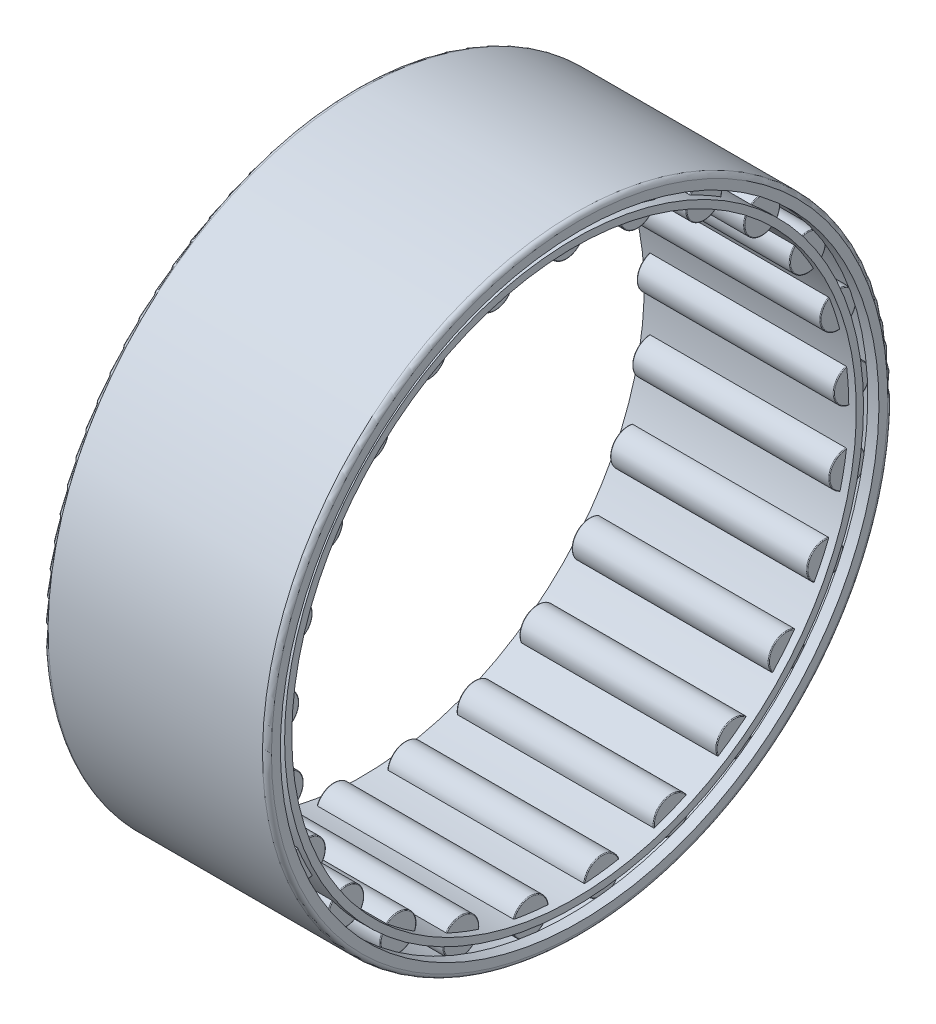
SolidWorks part; units mm, degrees
ref_plane "Plane1" through (0, 0, 0) normal (0, 0, 1) x (1, 0, 0)
ref_plane "Plane2" through (0, 0, 0) normal (0, 1, 0) x (1, 0, 0)
ref_plane "Plane3" through (0, 0, 0) normal (1, 0, 0) x (0, 0, -1)
sketch "Clipboard" plane through (0, 0, 0) normal (0, 0, 1) x (1, 0, 0)
  line L0 (-10, 0) -> (10, 0) construction
  line L1 (0, 0) -> (20.2657, -9.45)
  line L2 (0, 0) -> (36.8323, 17.1752)
  line L3 (0, 0) -> (20.2657, -9.45)
  line L4 (0, 0) -> (-76.2, -2.661)
  dimension "BallCLRad" = 40.64
  dimension "Bore" = 76.2
sketch "InnRacSke" plane through (0, 0, 0) normal (0, 0, 1) x (1, 0, 0)
  line L0 (-14.2875, 42.545) -> (-15.875, 42.545)
  line L1 (-15.875, 42.545) -> (-15.875, 43.815)
  line L2 (-15.24, 44.45) -> (15.24, 44.45)
  line L4 (15.875, 43.815) -> (15.875, 42.545)
  line L5 (15.875, 42.545) -> (14.2875, 42.545)
  line L6 (14.2875, 42.545) -> (14.2875, 43.18)
  line L7 (14.2875, 43.18) -> (-14.2875, 43.18)
  line L8 (-14.2875, 43.18) -> (-14.2875, 42.545)
  line L9 (-31.75, 0) -> (31.75, 0) construction
  arc A0 (-15.875, 43.815) -> (-15.24, 44.45) centre (-15.24, 43.815) cw
  arc A2 (15.24, 44.45) -> (15.875, 43.815) centre (15.24, 43.815) cw
  dimension "D1" = 86.36
revolve "Race" add sketch "InnRacSke" angle 360 about L9 reverse direction yes
sketch "RolDetSke" plane through (0, 0, 0) normal (0, 0, 1) x (1, 0, 0)
  line L0 (-14.0018, 43.0906) -> (-14.0017, 40.64)
  line L1 (-14.0017, 40.64) -> (14.0017, 40.64)
  line L2 (14.0017, 40.64) -> (14.0018, 43.0906)
  line L3 (13.8996, 43.1927) -> (-13.8996, 43.1927)
  line L4 (-28.575, 40.64) -> (28.575, 40.64) construction
  arc A0 (14.0018, 43.0906) -> (13.8996, 43.1927) centre (13.8996, 43.0906) ccw
  arc A1 (-13.8996, 43.1927) -> (-14.0018, 43.0906) centre (-13.8996, 43.0906) ccw
  dimension "Roller_length" = 28.0035
revolve "RollerDetailed" add sketch "RolDetSke" angle 360 about L4 reverse direction yes
ref_axis "Axis1" through (-50, 0, 0) along (1, 0, 0)
sketch "CagSpiSke" plane through (0, 0, 0) normal (0, 0, 1) x (1, 0, 0)
  line L0 (15.0812, 40.1295) -> (15.0812, 41.1505)
  line L1 (15.0812, 41.1505) -> (-15.0813, 41.1505)
  line L2 (-15.0813, 41.1505) -> (-15.0813, 40.1295)
  line L3 (-15.0813, 40.1295) -> (15.0812, 40.1295)
  line L4 (-31.75, 0) -> (31.75, 0) construction
  dimension "D2" = 80.2589
  dimension "halfWidth" = 15.0812
revolve "CageSpine" add sketch "CagSpiSke" angle 360 about L4
pattern_circular "RollersDetailed" count 25 every 14.4 about axis through (-50, 0, 0) along (1, 0, 0) of "RollerDetailed"
sketch "RolSimSke" plane through (0, 0, 0) normal (0, 0, 1) x (1, 0, 0)
  line L0 (-25.4, 0) -> (25.4, 0) construction
  line L2 (-13.8996, 43.2054) -> (13.8996, 43.2054)
  line L3 (-14.0018, 43.1033) -> (-14.0018, 38.2021)
  line L4 (-13.8996, 38.1) -> (13.8996, 38.1)
  line L5 (14.0017, 43.1033) -> (14.0017, 38.2021)
  arc A0 (-14.0018, 38.2021) -> (-13.8996, 38.1) centre (-13.8996, 38.2021) ccw
  arc A1 (-13.8996, 43.2054) -> (-14.0018, 43.1033) centre (-13.8996, 43.1033) ccw
  arc A2 (14.0017, 43.1033) -> (13.8996, 43.2054) centre (13.8996, 43.1033) ccw
  arc A3 (13.8996, 38.1) -> (14.0017, 38.2021) centre (13.8996, 38.2021) ccw
  point P10 (-14.0018, 38.1)
  point P15 (14.0017, 43.2054)
  point P18 (14.0017, 38.1)
  dimension "D1" = 0.1021
  dimension "Bore" = 76.2
  dimension "Roller_length" = 28.0035
  dimension "Roller_diameter" = 5.1054
  dimension "halfWidth" = 14.0017
revolve "RollersSimplified" [suppressed] add sketch "RolSimSke" angle 360 about L0
equation "\"BallCLRad@Clipboard\" =  ( \"D1@InnRacSke\" + \"Bore@Clipboard\" )  / 4"
equation "\"RollerCLRad@RolDetSke\" = \"BallCLRad@Clipboard\""
equation "\"halfCyl@InnRacSke\" = \"Cyl_Len@InnRacSke\" / 2"
equation "\"Roller_length@RolDetSke\" = \"Cyl_Len@InnRacSke\" * .98"
equation "\"halfLength@RolDetSke\" = \"Roller_length@RolDetSke\" / 2"
equation "\"Roller_diameter@RolDetSke\" =  ( \"D1@InnRacSke\" - \"Bore@Clipboard\" )  / 2 + .001"
equation "\"Roller_radius@RolDetSke\" = \"Roller_diameter@RolDetSke\" / 50"
equation "\"Cage_width@CagSpiSke\" =  ( \"Cyl_Len@InnRacSke\" + \"Width@InnRacSke\" )  / 2"
equation "\"halfWidth@CagSpiSke\" = \"Cage_width@CagSpiSke\" / 2"
equation "\"Cage_thickness@CagSpiSke\"  = \"Roller_diameter@RolDetSke\" / 5"
equation "\"D2@CagSpiSke\" =  \"RollerCLRad@RolDetSke\" * 2 - \"Cage_thickness@CagSpiSke\""
equation "\"Roller_length@RolSimSke\" = \"Cyl_Len@InnRacSke\" * .98"
equation "\"halfWidth@RolSimSke\" = \"Roller_length@RolSimSke\" / 2"
equation "\"D1@RolSimSke\" = \"Roller_radius@RolDetSke\""
equation "\"Roller_diameter@RolSimSke\" =  ( \"D1@InnRacSke\" - \"Bore@Clipboard\" )  / 2 + .001"
equation "\"Bore@RolSimSke\" = \"Bore@Clipboard\""
equation "\"Max_count@Clipboard\" = int( 3.14159265 / atn(( \"Roller_diameter@RolDetSke\" / 2) / sqr( \"RollerCLRad@RolDetSke\"  *  \"RollerCLRad@RolDetSke\" - ( \"Roller_diameter@RolDetSke\" / 2) *  ( \"Roller_diameter@RolDetSke\" / 2))))"
equation "\"Max_count@Clipboard\" = ((sgn( \"Max_count@Clipboard\" - \"Count@Clipboard\" )-1)*( \"Max_count@Clipboard\" - \"Count@Clipboard\" ))/-2+ \"Count@Clipboard\""
equation "\"Count@RollersDetailed\" = int( \"Show_count@Clipboard\" ) "
equation "\"Count@RollersDetailed\" = ((sgn( \"Count@RollersDetailed\" - \"Max_count@Clipboard\" )-1)*( \"Count@RollersDetailed\" - \"Max_count@Clipboard\" ))/-2+ \"Max_count@Clipboard\""
equation "\"Count@RollersDetailed\" = ((sgn( \"Count@RollersDetailed\" - \"Min_count@Clipboard\" )+1)*( \"Count@RollersDetailed\" - \"Min_count@Clipboard\"))/2 +\"Min_count@Clipboard\""
equation "\"Angle@RollersDetailed\" = 360.0 / \"Max_count@Clipboard\""
equation "\"Angle@CageSpine\" =  \"Angle@RollersDetailed\" * ( \"Count@RollersDetailed\" -1 + int( \"Count@RollersDetailed\" / \"Max_count@Clipboard\" ) )  + 0.001 -  int( \"Count@RollersDetailed\" / \"Max_count@Clipboard\" ) * 0.001"
equation "\"Angle@CageSpine\" =  \"Angle@CageSpine\" * int( \"Min_count@Clipboard\" / 2) + int(1 / \"Min_count@Clipboard\")  * 0.001"
